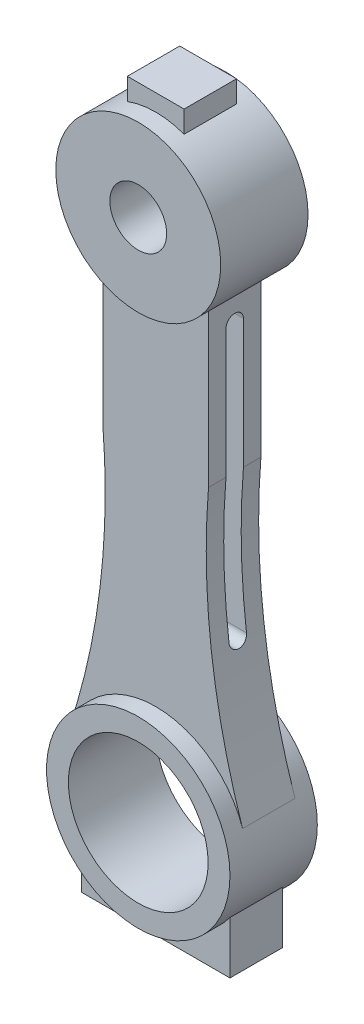
SolidWorks part; units mm, degrees
ref_plane "Ön Düzlem" through (0, 0, 0) normal (0, 0, 1) x (1, 0, 0)
ref_plane "Üst Düzlem" through (0, 0, 0) normal (0, 1, 0) x (1, 0, 0)
ref_plane "Sağ Düzlem" through (0, 0, 0) normal (1, 0, 0) x (0, 0, -1)
sketch "Çizim2" plane through (0, 0, 0) normal (0, 0, 1) x (1, 0, 0)
  line L0 (0, 0) -> (0, -120) construction
  line L1 (-12.0829, -14.5065) -> (-12.0829, -49.5065)
  line L2 (12.0829, -14.5065) -> (12.0829, -49.5065)
  line L4 (-17, -132.3288) -> (-17, -144.3288)
  line L5 (17, -132.3288) -> (17, -144.3288)
  line L6 (-17, -144.3288) -> (17, -144.3288)
  line L8 (-6.5, 17.7252) -> (-6.5, 22.7252)
  line L9 (6.5, 17.7252) -> (6.5, 22.7252)
  line L10 (-6.5, 22.7252) -> (6.5, 22.7252)
  circle A0 centre (0, 0) radius 6.5
  circle A1 centre (0, 0) radius 18.8795
  circle A2 centre (0, -120) radius 16
  circle A3 centre (0, -120) radius 21
  arc A4 (-12.0829, -49.5065) -> (-19.8883, -113.2578) centre (-171.5256, -62.3386) cw
  arc A5 (12.0829, -49.5065) -> (19.8883, -113.2578) centre (171.5256, -62.3386) ccw
  dimension "D3" = 32
  dimension "D4" = 42
  dimension "D5" = 120
  dimension "D6" = 35
  dimension "D8" = 12
  dimension "D9" = 34
extrude "Yükseklik-Ekstrüzyon1" add sketch "Çizim2" along normal mid plane 20 contours A0 A1 | A3 A2 region at (-18.0763, 3.131, 0) region at (0, -99.594, 0)
extrude "Yükseklik-Ekstrüzyon3" add sketch "Çizim2<8>" along normal mid plane 12 contours A1 L0 A3 A5 L2 | L0 A1 L1 A4 A3 region at (6.6025, -61.2778, 0) region at (-6.6025, -61.2778, 0)
sketch "Çizim2<8>" plane through (0, 0, 0) normal (0, 0, 1) x (1, 0, 0) same geometry as "Çizim2"
extrude "Yükseklik-Ekstrüzyon4" add sketch "Çizim2<9>" along normal mid plane 12 contours A1 L9 L10 L8 | A3 L4 L6 L5 region at (0, 20.5985, 0) region at (0, -141.3606, 0)
sketch "Çizim2<9>" plane through (0, 0, 0) normal (0, 0, 1) x (1, 0, 0) same geometry as "Çizim2"
sketch "Çizim4" plane through (0, 0, 0) normal (1, 0, 0) x (0, 0, -1)
  line L0 (0, -20) -> (0, -82) construction
  line L1 (2, -20) -> (2, -82)
  line L2 (-2, -20) -> (-2, -82)
  arc A0 (2, -20) -> (-2, -20) centre (0, -20) ccw
  arc A1 (-2, -82) -> (2, -82) centre (0, -82) ccw
  point P3 (0, -51)
  dimension "D1" = 4
  dimension "D2" = 62
  dimension "D3" = 20
extrude "Kes-Ekstrüzyon1" cut sketch "Çizim4" along normal through all from offset 6
mirror "Aynalama1" about plane through (0, 0, 0) normal (1, 0, 0) of "Kes-Ekstrüzyon1"
